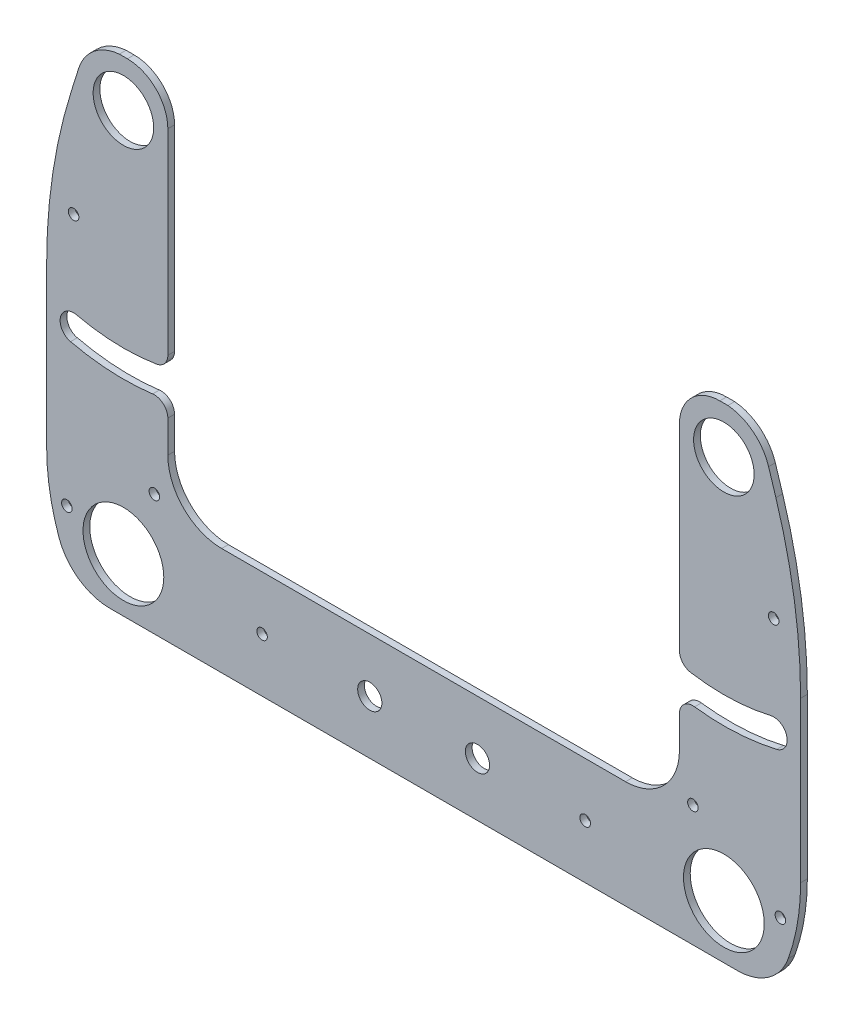
SolidWorks part; units mm, degrees
material "6061 Alloy"
ref_plane "Front Plane" through (0, 0, 0) normal (0, 0, 1) x (1, 0, 0)
ref_plane "Top Plane" through (0, 0, 0) normal (0, 1, 0) x (1, 0, 0)
ref_plane "Right Plane" through (0, 0, 0) normal (1, 0, 0) x (0, 0, -1)
sketch "Sketch1" plane through (0, 0, 0) normal (0, 0, 1) x (1, 0, 0)
  line L5 (120.65, -152.4) -> (120.65, -6.35)
  line L6 (127, 0) -> (171.45, 0) construction
  line L7 (177.8, -6.35) -> (177.8, -222.25)
  line L10 (0, -206.2199) -> (0, -63.6275) construction
  line L11 (-54.9244, 0) -> (300.6756, 0) construction
  line L13 (12.7, -177.8) -> (95.25, -177.8)
  line L14 (12.7, -228.6) -> (171.45, -228.6)
  line L15 (141.605, -22.0269) -> (141.605, -80.9091) construction
  line L16 (141.605, -22.0269) -> (141.605, -123.6269) construction
  line L19 (-141.605, -19.05) -> (-141.605, -77.9322) construction
  line L20 (141.605, -22.0269) -> (141.605, -203.2) construction
  line L22 (-120.65, -152.4) -> (-120.65, -6.35)
  line L23 (-12.7, -177.8) -> (-95.25, -177.8)
  line L24 (-12.7, -228.6) -> (-171.45, -228.6)
  line L25 (-177.8, -6.35) -> (-177.8, -222.25)
  line L26 (-12.7, -177.8) -> (12.7, -177.8)
  line L27 (-12.7, -228.6) -> (12.7, -228.6)
  line L28 (-177.8, -6.35) -> (-177.8, 6.35)
  line L29 (-165.1, 19.05) -> (-133.35, 19.05)
  line L30 (-120.65, 6.35) -> (-120.65, -6.35)
  line L31 (120.65, 6.35) -> (120.65, -6.35)
  line L32 (177.8, -6.35) -> (177.8, 6.35)
  line L33 (165.1, 19.05) -> (133.35, 19.05)
  arc A0 (95.25, -177.8) -> (120.65, -152.4) centre (95.25, -152.4) ccw
  arc A4 (120.65, -6.35) -> (127, 0) centre (127, -6.35) cw construction
  circle A8 centre (141.605, -22.0269) radius 14.2875
  circle A9 centre (141.605, -22.0269) radius 38.1 construction
  arc A10 (177.8, -6.35) -> (171.45, 0) centre (171.45, -6.35) ccw construction
  arc A11 (171.45, -228.6) -> (177.8, -222.25) centre (171.45, -222.25) ccw
  arc A14 (141.605, -79.1769) -> (120.9214, -75.3027) centre (141.605, -22.0269) ccw construction
  arc A15 (-141.605, -79.1769) -> (-120.9214, -75.3027) centre (-141.605, -22.0269) cw construction
  circle A16 centre (-141.605, -22.0269) radius 38.1 construction
  circle A17 centre (-141.605, -22.0269) radius 14.2875
  arc A19 (-95.25, -177.8) -> (-120.65, -152.4) centre (-95.25, -152.4) cw
  circle A20 centre (141.605, -123.6269) radius 38.1 construction
  circle A21 centre (-141.605, -123.6269) radius 38.1 construction
  arc A23 (-171.45, -228.6) -> (-177.8, -222.25) centre (-171.45, -222.25) cw
  circle A24 centre (-141.605, -203.2) radius 19.05
  circle A37 centre (141.605, -203.2) radius 19.05
  circle A39 centre (-76.2, -203.2) radius 2.4892
  circle A40 centre (76.2, -203.2) radius 2.4892
  circle A42 centre (-25.4, -203.2) radius 5.715
  arc A44 (-133.35, 19.05) -> (-120.65, 6.35) centre (-133.35, 6.35) cw
  arc A45 (-177.8, 6.35) -> (-165.1, 19.05) centre (-165.1, 6.35) cw
  arc A46 (133.35, 19.05) -> (120.65, 6.35) centre (133.35, 6.35) ccw
  arc A47 (177.8, 6.35) -> (165.1, 19.05) centre (165.1, 6.35) ccw
  circle A50 centre (-149.225, 6.35) radius 2.4892
  circle A53 centre (149.225, 6.35) radius 2.4892
  circle A54 centre (-168.275, -196.85) radius 2.4892
  circle A56 centre (168.275, -196.85) radius 2.4892
  circle A58 centre (-165.1, -76.2) radius 2.4892
  circle A59 centre (165.1, -76.2) radius 2.4892
  circle A60 centre (-127, -171.45) radius 2.4892
  circle A61 centre (127, -171.45) radius 2.4892
  circle A62 centre (25.4, -203.2) radius 5.715
  point P2 (177.8, -44.45)
  point P18 (177.8, 0)
  point P23 (177.8, -228.6)
  point P24 (177.8, -228.6)
  point P31 (177.8, 0)
  point P48 (-177.8, 0)
  point P49 (-177.8, -228.6)
  point P51 (-177.8, -44.45)
  point P78 (-141.605, -203.2)
  dimension "D6" = 25.4
  dimension "D7" = 6.35
  dimension "D8" = 6.35
  dimension "D9" = 177.8
  dimension "D10" = 28.575
  dimension "D12" = 76.2
  dimension "D13" = 57.15
  dimension "D15" = 38.1
  dimension "D18" = 76.2
  dimension "D21" = 4.9784
  dimension "D29" = 9.525
  dimension "D32" = 4.9784
  dimension "D35" = 11.43
  dimension "D40" = 12.7
  dimension "D43" = 4.9784
  dimension "D45" = 12.7
  dimension "D30" = 4.9784
  dimension "D41" = 4.9784
  dimension "D22" = 6.35
  dimension "D2" = 120.65
  dimension "D3" = 177.8
  dimension "D4" = 228.6
  dimension "D5" = 177.8
  dimension "D11" = 20.955
  dimension "`" = 22.0269
  dimension "D14" = 57.15
  dimension "D16" = 184.15
  dimension "D17" = 101.6
  dimension "D19" = 25.4
  dimension "D20" = 101.6
  dimension "D23" = 57.15
  dimension "D25" = 25.4
  dimension "D26" = 31.75
  dimension "D27" = 25.4
  dimension "D28" = 25.4
  dimension "D31" = 25.4
  dimension "D33" = 12.7
  dimension "D34" = 25.4
  dimension "D39" = 19.05
  dimension "D44" = 28.575
  dimension "D24" = 95.25
extrude "Boss-Extrude3" add sketch "Sketch1" along normal blind 3.175
sketch "Sketch2" plane through (0, 0, 3.175) normal (0, 0, 1) x (1, 0, 0)
  line L0 (177.8, -222.25) -> (177.8, 6.35) construction
  line L1 (-177.8, 19.05) -> (177.8, 19.05)
  line L2 (-177.8, 19.05) -> (-177.8, 0)
  line L3 (-177.8, 0) -> (177.8, 0)
  line L4 (177.8, 19.05) -> (177.8, 0)
  line L5 (-177.8, 6.35) -> (-177.8, -222.25) construction
  line L7 (-133.35, 19.05) -> (-165.1, 19.05) construction
  dimension "D1" = 19.05
extrude "Cut-Extrude1" cut sketch "Sketch2" against normal through all
fillet "Fillet1" radius 19.05 4 edges at (177.8, 0, 1.5875) (120.65, 0, 1.5875) (-120.65, 0, 1.5875) (-177.8, 0, 1.5875)
sketch "Sketch3" plane through (0, 0, 3.175) normal (0, 0, 1) x (1, 0, 0)
  line L2 (-177.8, -19.05) -> (-177.8, -222.25) construction
  line L3 (-158.75, 0) -> (-139.7, 0) construction
  line L4 (-177.8, -63.5) -> (-177.8, 0)
  line L5 (-177.8, 0) -> (-139.7, 0)
  line L6 (-177.8, -63.5) -> (-162.6988, -15.4039)
  arc A3 (-139.7, 0) -> (-162.6988, -15.4039) centre (-141.605, -22.0269) ccw
  arc M14 (-158.75, 0) -> (-177.8, -19.05) centre (-158.75, -19.05) ccw
  line M15 (-177.8, -19.05) -> (-177.8, -222.25)
  dimension "D1" = 63.5
extrude "Cut-Extrude2" cut sketch "Sketch3" against normal through all contours A3 L5 M14 M15 | L5 L4 M14 region at (-169.5998, -21.9282, 3.175) region at (-173.5448, -4.2552, 3.175)
ref_plane "Plane1" through (0, 0, 0) normal (-1, 0, 0) x (0, 0, 1)
mirror "Mirror1" about plane through (0, 0, 0) normal (-1, 0, 0) of "Cut-Extrude2"
fillet "Fillet2" radius 254 2 edges at (177.8, -63.5, 1.5875) (-177.8, -63.5, 1.5875)
sketch "Sketch4" plane through (0, 0, 3.175) normal (0, 0, 1) x (1, 0, 0)
  line L0 (0, -177.8) -> (0, -13.685) construction
  line L5 (-177.8, -102.4383) -> (-177.8, -222.25) construction
  line L6 (-171.45, -228.6) -> (171.45, -228.6) construction
  line L7 (-177.8, -177.8) -> (-177.8, -228.6)
  line L8 (-177.8, -228.6) -> (-164.1882, -228.6)
  line L9 (177.8, -177.8) -> (177.8, -228.6)
  line L10 (177.8, -228.6) -> (164.1882, -228.6)
  circle A0 centre (-76.2, -177.8) radius 101.6 construction
  arc A1 (-177.8, -177.8) -> (-164.1882, -228.6) centre (-76.2, -177.8) ccw
  arc A2 (177.8, -177.8) -> (164.1882, -228.6) centre (76.2, -177.8) cw
  dimension "D1" = 203.2
  dimension "D2" = 50.8
extrude "Cut-Extrude3" cut sketch "Sketch4" against normal through all contours L8 A1 L7 | L9 L10 A2
fillet "Fillet3" radius 25.4 2 edges at (164.1882, -228.6, 1.5875) (-164.1882, -228.6, 1.5875)
sketch "Sketch5" plane through (0, 0, 3.175) normal (0, 0, 1) x (1, 0, 0)
  line L2 (-120.65, -129.7962) -> (-120.65, -116.8262)
  line L5 (120.65, -129.7962) -> (120.65, -116.8262)
  line L6 (120.65, -19.05) -> (120.65, -152.4) construction
  line L7 (177.8, -177.8) -> (177.8, -102.4383) construction
  line L8 (0, -203.7675) -> (0, -15.567) construction
  circle A4 centre (141.605, -22.0269) radius 103.4377 construction
  arc A5 (120.65, -116.8262) -> (163.6577, -116.5769) centre (141.605, -22.0269) ccw
  arc A6 (120.65, -129.7962) -> (166.5423, -128.9449) centre (141.605, -22.0269) ccw
  arc A9 (166.5423, -128.9449) -> (163.6577, -116.5769) centre (165.1, -122.7609) ccw
  arc A10 (-120.65, -129.7962) -> (-166.5423, -128.9449) centre (-141.605, -22.0269) cw
  arc A11 (-120.65, -116.8262) -> (-163.6577, -116.5769) centre (-141.605, -22.0269) cw
  arc A12 (-166.5423, -128.9449) -> (-163.6577, -116.5769) centre (-165.1, -122.7609) cw
  dimension "D1" = 97.0877
  dimension "D2" = 109.7877
  dimension "D4" = 12.7
  dimension "D3" = 206.8754
extrude "Cut-Extrude4" cut sketch "Sketch5" against normal through all contours A10 A12 A11 L2 | A9 A5 L5 A6
fillet "Fillet4" radius 6.35 4 edges at (120.65, -129.7962, 1.5875) (120.65, -116.8262, 1.5875) (-120.65, -129.7962, 1.5875) (-120.65, -116.8262, 1.5875)
sketch "Sketch6" plane through (0, 0, 0) normal (0, 0, -1) x (-1, 0, 0)
  line L1 (-743.0643, -231.14) -> (49256.9357, -231.14) construction
  line L2 (-180.34, -1269.6837) -> (-180.34, 48730.3163) construction
  line L3 (148.042, -228.6) -> (-148.042, -228.6) construction
  circle A0 centre (-76.2, -203.2) radius 2.4892 construction
  point P11 (-180.34, -231.14)
  dimension "D3" = 104.14
  dimension "D1" = 2.54
